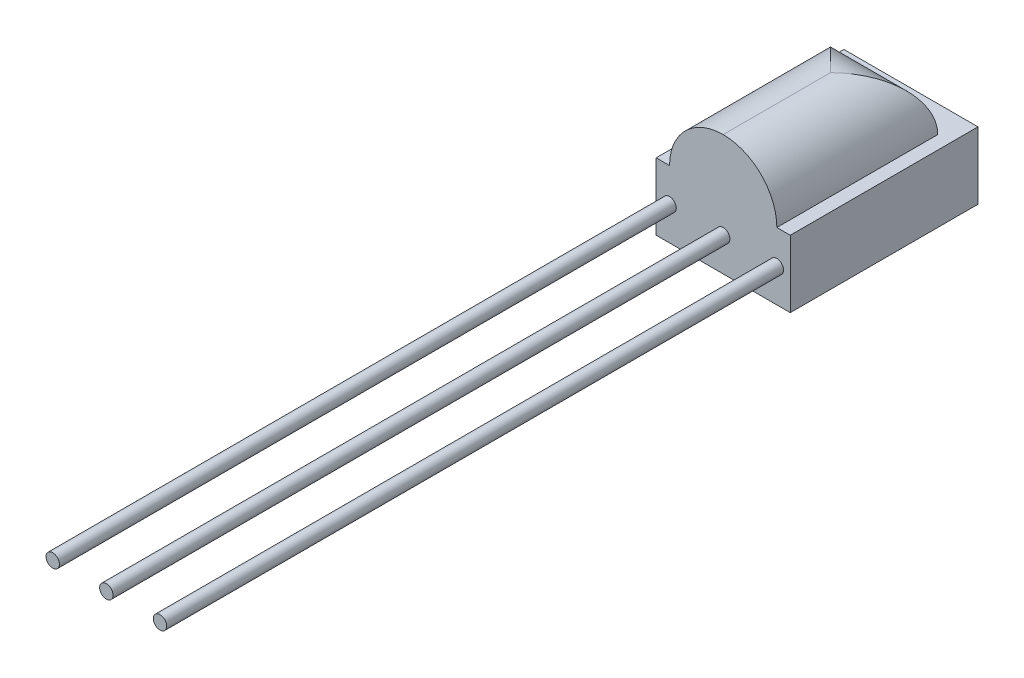
SolidWorks part; units mm, degrees
ref_plane "Plan de face" through (0, 0, 0) normal (0, 0, 1) x (1, 0, 0)
ref_plane "Plan de dessus" through (0, 0, 0) normal (0, 1, 0) x (1, 0, 0)
ref_plane "Plan de droite" through (0, 0, 0) normal (1, 0, 0) x (0, 0, -1)
sketch "Esquisse1" plane through (0, 0, 0) normal (0, 1, 0) x (1, 0, 0)
  line L1 (0, 0) -> (5, 0)
  line L2 (0, 0) -> (0, 7)
  line L3 (0, 7) -> (5, 7)
  line L4 (5, 0) -> (5, 7)
  dimension "D1" = 7
  dimension "D2" = 5
extrude "Boss.-Extru.1" add sketch "Esquisse1" along normal blind 2.5
sketch "Esquisse2" plane through (0, 0, 0) normal (0, 0, 1) x (1, 0, 0)
  line L0 (5, 2.5) -> (5, 0) construction
  line L1 (0, 2.5) -> (0, 0) construction
  line L2 (0, 0) -> (5, 0) construction
  circle A0 centre (0.5, 1.25) radius 0.25
  circle A1 centre (2.5, 1.25) radius 0.25
  circle A2 centre (4.5, 1.25) radius 0.25
  dimension "D1" = 0.5
  dimension "D2" = 0.5
  dimension "D3" = 0.5
  dimension "D4" = 2.5
  dimension "D5" = 0.5
  dimension "D6" = 0.5
  dimension "D7" = 1.25
  dimension "D8" = 1.25
  dimension "D9" = 1.25
extrude "Boss.-Extru.2" add sketch "Esquisse2" along normal blind 23
sketch "Esquisse3" plane through (0, 2.5, 0) normal (0, 1, 0) x (1, 0, 0)
  line L0 (0, 0) -> (5, 0) construction
  line L1 (0.5, 6) -> (4.5, 6)
  line L2 (0.5, 6) -> (0.5, 0)
  line L3 (0.5, 0) -> (4.5, 0)
  line L4 (4.5, 6) -> (4.5, 0)
  line L5 (0, 7) -> (0, 0) construction
  dimension "D1" = 6
  dimension "D2" = 4
  dimension "D3" = 0.5
extrude "Boss.-Extru.3" add sketch "Esquisse3" along normal blind 2
fillet "Congé1" radius 2 3 edges at (4.5, 4.5, -3) (2.5, 4.5, -6) (0.5, 4.5, -3)
